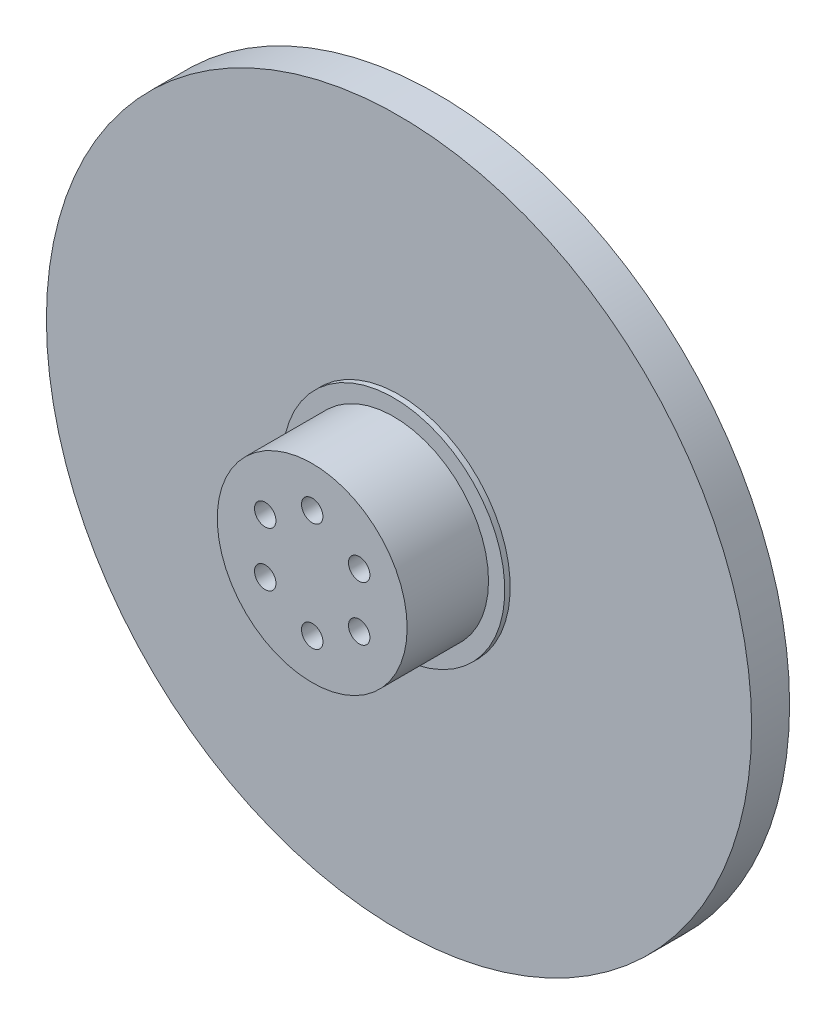
SolidWorks part; units mm, degrees
ref_plane "Front Plane" through (0, 0, 0) normal (0, 0, 1) x (1, 0, 0)
ref_plane "Top Plane" through (0, 0, 0) normal (0, 1, 0) x (1, 0, 0)
ref_plane "Right Plane" through (0, 0, 0) normal (1, 0, 0) x (0, 0, -1)
sketch "Sketch1" plane through (0, 0, 0) normal (0, 0, 1) x (1, 0, 0)
  circle A0 centre (0, 0) radius 17.5
  dimension "D1" = 35
extrude "Boss-Extrude1" add sketch "Sketch1" along normal blind 15
sketch "Sketch7" plane through (0, 0, 0) normal (0, 0, -1) x (-1, 0, 0)
  circle A0 centre (0, 0) radius 20.5
  dimension "D1" = 41
extrude "Boss-Extrude3" add sketch "Sketch7" along normal blind 1
sketch "Sketch3" plane through (0, 0, -1) normal (0, 0, -1) x (-1, 0, 0)
  circle A0 centre (0, 0) radius 65
  dimension "D1" = 130
extrude "Boss-Extrude2" add sketch "Sketch3" along normal blind 7
sketch "Sketch4" plane through (0, 0, -8) normal (0, 0, -1) x (-1, 0, 0)
  circle A0 centre (0, 0) radius 11
  dimension "D1" = 22
extrude "Cut-Extrude1" cut sketch "Sketch4" against normal blind 7
sketch "Sketch5" plane through (0, 0, -1) normal (0, 0, -1) x (-1, 0, 0)
  circle A0 centre (0, 0) radius 7.5
  dimension "D1" = 15
extrude "Cut-Extrude2" cut sketch "Sketch5" against normal blind 0.5
sketch "Sketch6" plane through (0, 0, 15) normal (0, 0, 1) x (1, 0, 0)
  circle A0 centre (0, 10) radius 1.975
  dimension "D1" = 3.95
  dimension "D2" = 10
extrude "Cut-Extrude3" cut sketch "Sketch6" against normal blind 6
pattern_circular "CirPattern1" count 6 over 360 about axis through (0, 0, 15) along (0, 0, 1) of "Cut-Extrude3"
